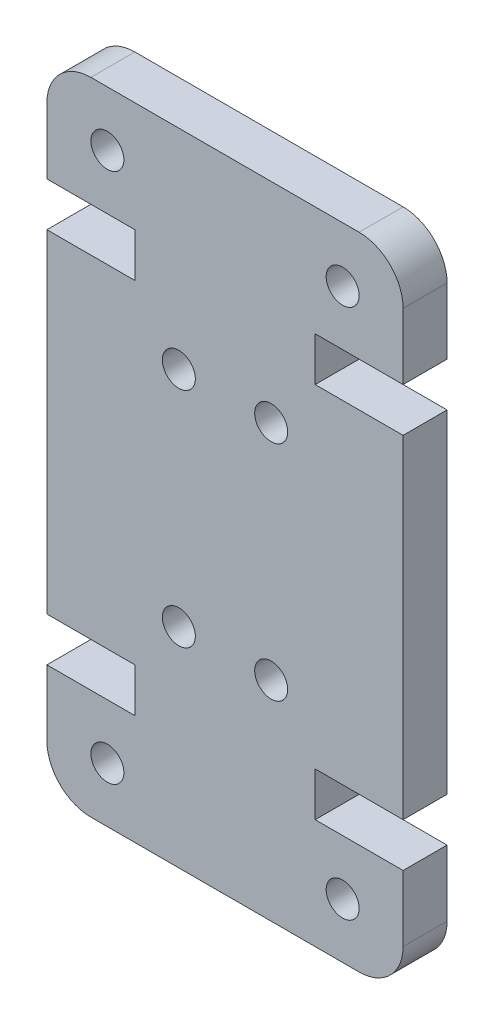
SolidWorks part; units mm, degrees
ref_plane "Front Plane" through (0, 0, 0) normal (0, 0, 1) x (1, 0, 0)
ref_plane "Top Plane" through (0, 0, 0) normal (0, 1, 0) x (1, 0, 0)
ref_plane "Right Plane" through (0, 0, 0) normal (1, 0, 0) x (0, 0, -1)
sketch "Sketch1" plane through (0, 0, 0) normal (0, 0, 1) x (1, 0, 0)
  line L0 (0, 22.14) -> (0, 7)
  line L1 (16.2, 22.14) -> (16.2, 7)
  line L2 (2, 29.14) -> (14.2, 29.14)
  line L3 (2, 0) -> (14.2, 0)
  line L4 (4, 24.14) -> (4, 22.14)
  line L5 (0, 24.14) -> (4, 24.14)
  line L6 (4, 22.14) -> (0, 22.14)
  line L7 (4, 7) -> (4, 5)
  line L8 (0, 27.14) -> (0, 24.14)
  line L9 (16.2, 24.14) -> (16.2, 27.14)
  line L10 (0, 7) -> (4, 7)
  line L11 (12.2, 24.14) -> (12.2, 22.14)
  line L12 (4, 5) -> (0, 5)
  line L13 (12.2, 22.14) -> (16.2, 22.14)
  line L14 (16.2, 24.14) -> (12.2, 24.14)
  line L15 (12.2, 7) -> (12.2, 5)
  line L16 (0, 2) -> (0, 5)
  line L17 (16.2, 5) -> (16.2, 2)
  line L18 (12.2, 5) -> (16.2, 5)
  line L19 (16.2, 7) -> (12.2, 7)
  arc A0 (16.2, 27.14) -> (14.2, 29.14) centre (14.2, 27.14) ccw
  arc A1 (2, 29.14) -> (0, 27.14) centre (2, 27.14) ccw
  circle A2 centre (10.2, 19.64) radius 0.75
  circle A3 centre (6, 19.64) radius 0.75
  arc A4 (14.2, 0) -> (16.2, 2) centre (14.2, 2) ccw
  arc A5 (0, 2) -> (2, 0) centre (2, 2) ccw
  circle A6 centre (10.2, 9.5) radius 0.75
  circle A7 centre (6, 9.5) radius 0.75
  circle A8 centre (13.45, 2.5) radius 0.75
  circle A9 centre (2.75, 2.5) radius 0.75
  circle A10 centre (13.45, 26.64) radius 0.75
  circle A11 centre (2.75, 26.64) radius 0.75
extrude "Boss-Extrude1" add sketch "Sketch1" along normal blind 2
